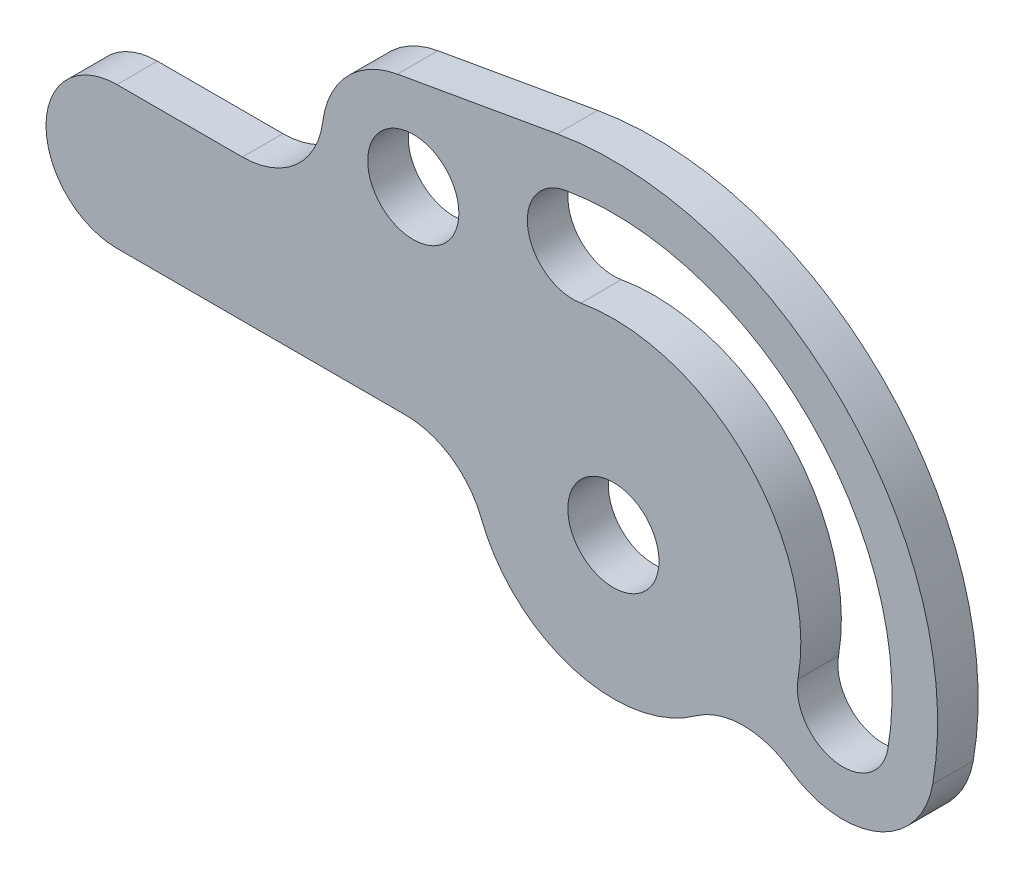
SolidWorks part; units mm, degrees
ref_plane "Front Plane" through (0, 0, 0) normal (0, 0, 1) x (1, 0, 0)
ref_plane "Top Plane" through (0, 0, 0) normal (0, 1, 0) x (1, 0, 0)
ref_plane "Right Plane" through (0, 0, 0) normal (1, 0, 0) x (0, 0, -1)
sketch "Sketch1" plane through (0, 0, 0) normal (0, 0, 1) x (1, 0, 0)
  line L0 (0, 0) -> (9.1281, 0) construction
  line L1 (0, 0) -> (0, 9.1281) construction
  line L2 (0, 0) -> (12.5071, -2.2053) construction
  line L3 (0, 0) -> (-2.2053, 12.5071) construction
  line L4 (-1.5851, 8.9894) -> (-7.8386, 7.8868) construction
  line L5 (0, 5.5562) -> (-22.225, 5.5562) construction
  line L6 (0, 0) -> (-22.225, 0) construction
  line L7 (-22.225, 0) -> (-22.225, 5.5562) construction
  line L8 (-19.4469, 5.5562) -> (-10.5454, 5.5562)
  line L9 (-19.4469, 0) -> (-5.5562, 0)
  line L10 (-7.2184, 4.3692) -> (-8.4589, 11.4044) construction
  line L11 (-8.4589, 11.4044) -> (-2.2053, 12.5071)
  circle A0 centre (0, 0) radius 1.7859
  circle A1 centre (0, 0) radius 5.5562
  circle A2 centre (0, 0) radius 9.1281 construction
  circle A3 centre (-1.5851, 8.9894) radius 1.7859
  circle A4 centre (8.9894, -1.5851) radius 1.7859
  circle A5 centre (-7.8386, 7.8868) radius 1.7859
  circle A6 centre (8.9894, -1.5851) radius 3.5719
  circle A7 centre (-1.5851, 8.9894) radius 3.5719
  circle A8 centre (-7.8386, 7.8868) radius 3.5719
  circle A9 centre (-19.4469, 2.7781) radius 2.7781
  arc A10 (7.2306, -1.275) -> (-1.275, 7.2306) centre (0, 0) ccw
  arc A11 (10.7483, -1.8952) -> (-1.8952, 10.7483) centre (0, 0) ccw
  arc A12 (12.5071, -2.2053) -> (-2.2053, 12.5071) centre (0, 0) ccw
  point P24 (-22.225, 2.7781)
  point P35 (-7.8386, 7.8868)
  dimension "D4" = 7.1437
  dimension "D5" = 11.1125
  dimension "D6" = 3.5719
  dimension "D1" = 6.35
  dimension "D2" = 10
  dimension "D3" = 10
  dimension "D7" = 22.225
extrude "Boss-Extrude1" add sketch "Sketch1" along normal blind 1.5875 contours A9 | A9 L9 A1 A7 A8 L8 | A1 A0 | A7 A8 A5 | A7 A8 | A11 A7 A8 A10 A3 | A6 A12 A7 A11 | A6 A10 A7 A1 | A11 A4 A10 A6 | A8 A7 L11 region at (-10.8715, 2.8236, 0) region at (-19.4469, 2.7781, 0) region at (-11.1087, 9.0535, 0) region at (-5.2386, 11.4257, 0) region at (-4.2118, 7.3361, 0) region at (-4.7118, 8.4381, 0) region at (-4.1359, 3.4705, 0) region at (8.8312, 8.8312, 0) region at (4.2073, 4.2073, 0) region at (6.1384, 0.4003, 0)
fillet "Fillet1" radius 3.175 3 edges at (5.4718, -0.9648, 0.7937) (-5.5562, 0, 0.7937) (-10.5454, 5.5562, 0.7937)
